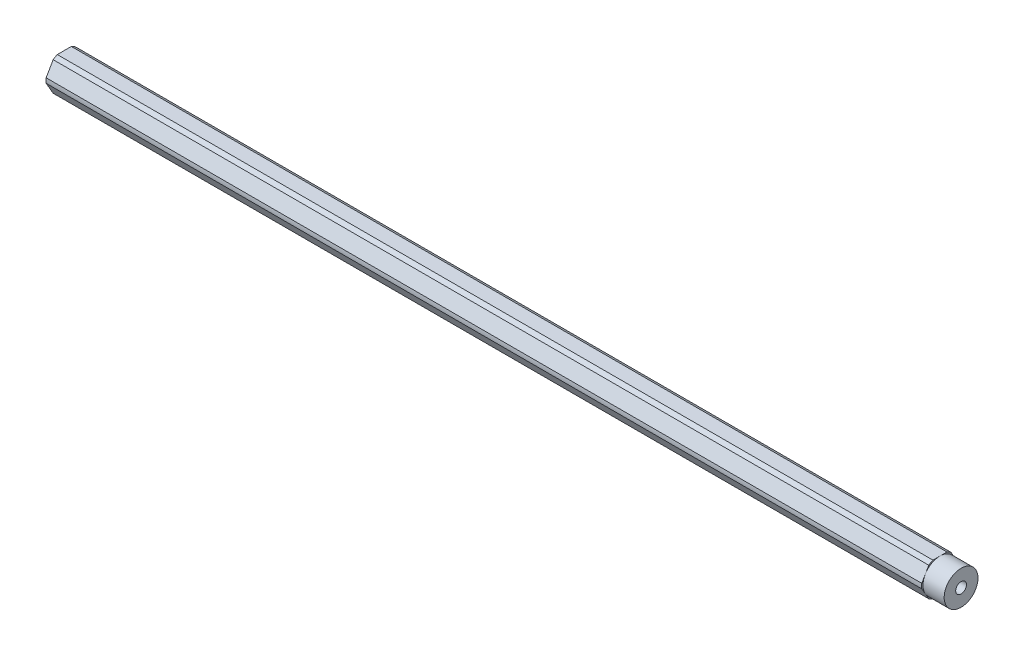
SolidWorks part; units mm, degrees
material "7075-T6 (SN)"
ref_plane "Front Plane" through (0, 0, 0) normal (0, 0, 1) x (1, 0, 0)
ref_plane "Top Plane" through (0, 0, 0) normal (0, 1, 0) x (1, 0, 0)
ref_plane "Right Plane" through (0, 0, 0) normal (1, 0, 0) x (0, 0, -1)
sketch "Sketch1" plane through (0, 0, 0) normal (1, 0, 0) x (0, 0, -1)
  line L1 (3.6662, 6.35) -> (-3.6662, 6.35)
  line L2 (-3.6662, 6.35) -> (-7.3323, 0)
  line L3 (-7.3323, 0) -> (-3.6662, -6.35)
  line L4 (-3.6662, -6.35) -> (3.6662, -6.35)
  line L5 (3.6662, -6.35) -> (7.3323, 0)
  line L6 (7.3323, 0) -> (3.6662, 6.35)
  circle A0 centre (0, 0) radius 6.875
  circle A1 centre (0, 0) radius 2.0193
  circle A2 centre (0, 0) radius 6.35 construction
  dimension "D1" = 12.7
  dimension "D2" = 13.75
  dimension "D3" = 4.0386
extrude "Boss-Extrude1" add sketch "Sketch1" along normal mid plane 336.55 contours L6 A0 L1 L2 L3 L4 L5 A1 region at (0, 5.7918, -3.3439)
hole_wizard "#10-32 Tapped Hole1" positions "3DSketch1" profile "Sketch2" tap size "#10-32" standard "ANSI Inch"
sketch3d "3DSketch1"
  circle A0 centre (-168.275, 0, 0) radius 2.0193 construction
  circle A1 centre (168.275, 0, 0) radius 2.0193 construction
  point P0 (168.275, 0, 0)
  point P2 (-168.275, 0, 0)
  point P7 (-166.2557, 0, 0)
  point P10 (170.2943, 0, 0)
sketch "Sketch2" plane through (168.275, 0, 0) normal (0, 1, 0) x (0, 0, -1)
  line L0 (0, 0) -> (0, 17.5608)
  line L1 (0, 17.5608) -> (2.0193, 16.3474)
  line L2 (2.0193, 16.3474) -> (2.0193, 0)
  line L5 (2.0193, 0) -> (0, 0)
  line L10 (0, 17.5608) -> (-2.0193, 16.3474) construction
  line L11 (0, -6.35) -> (0, 107.95) construction
  dimension "Tap Drill Dia." = 4.0386
  dimension "Tap Drill Depth" = 16.3474
  dimension "Drill Angle" = 118
cosmetic thread "Hole Thread1" parameters "D1"=13.97, "D2"=4.826
cosmetic thread "Hole Thread2" parameters "D1"=13.97, "D2"=4.826
sketch "Sketch3" plane through (168.275, 0, 0) normal (1, 0, 0) x (0, 0, -1)
  line L0 (6.8168, 0.893) -> (4.1818, 5.457) construction
  circle A0 centre (0, 0) radius 6.35
extrude "Cut-Extrude-Thin1" cut sketch "Sketch3" against normal blind 7.9375 thin thin type one direction wall 2.54
equation "\"D2@Sketch1\"=13.75mm"
